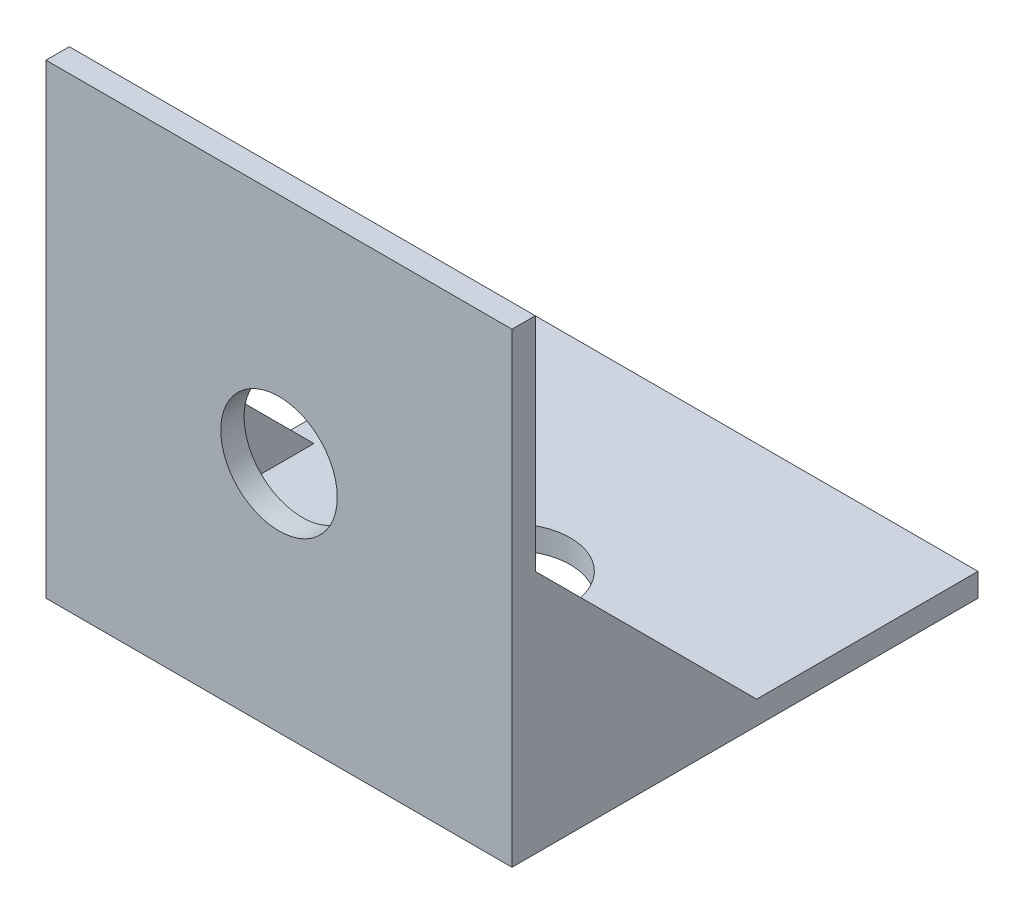
SolidWorks part; units mm, degrees
ref_plane "Front Plane" through (0, 0, 0) normal (0, 0, 1) x (1, 0, 0)
ref_plane "Top Plane" through (0, 0, 0) normal (0, 1, 0) x (1, 0, 0)
ref_plane "Right Plane" through (0, 0, 0) normal (1, 0, 0) x (0, 0, -1)
sketch "Sketch1" plane through (0, 0, 0) normal (0, 1, 0) x (1, 0, 0)
  line L1 (10, 10) -> (-10, 10)
  line L2 (10, 10) -> (10, -10)
  line L3 (10, -10) -> (-10, -10)
  line L4 (-10, 10) -> (-10, -10)
  line L5 (10, 10) -> (-10, -10) construction
  line L6 (10, -10) -> (-10, 10) construction
  circle A0 centre (0, 0) radius 2.5
  point P0 (0, 0)
  dimension "D1" = 20
  dimension "D2" = 20
extrude "Boss-Extrude1" add sketch "Sketch1" along normal blind 1
sketch "Sketch2" plane through (0, 0, 10) normal (0, 0, 1) x (1, 0, 0)
  line L1 (-10, 0) -> (10, 0)
  line L2 (-10, 0) -> (-10, 20)
  line L3 (-10, 20) -> (10, 20)
  line L4 (10, 0) -> (10, 20)
  circle A0 centre (0, 10) radius 2.5
extrude "Boss-Extrude2" add sketch "Sketch2" against normal blind 1
sketch "Sketch3" plane through (10, 0, 0) normal (1, 0, 0) x (0, 0, -1)
  line L0 (-9, 10.5) -> (0.5, 1)
  line L1 (-9, 1) -> (-9, 20) construction
  line L2 (-9, 1) -> (10, 1) construction
  line L3 (0.5, 1) -> (-9, 1)
  line L4 (-9, 1) -> (-9, 10.5)
extrude "Boss-Extrude3" add sketch "Sketch3" against normal blind 1
extrude "Boss-Extrude4" add sketch "Sketch3<2>" against normal blind 1 from offset 19 offset against normal yes
sketch "Sketch3<2>" plane through (10, 0, 0) normal (1, 0, 0) x (0, 0, -1) same geometry as "Sketch3"
